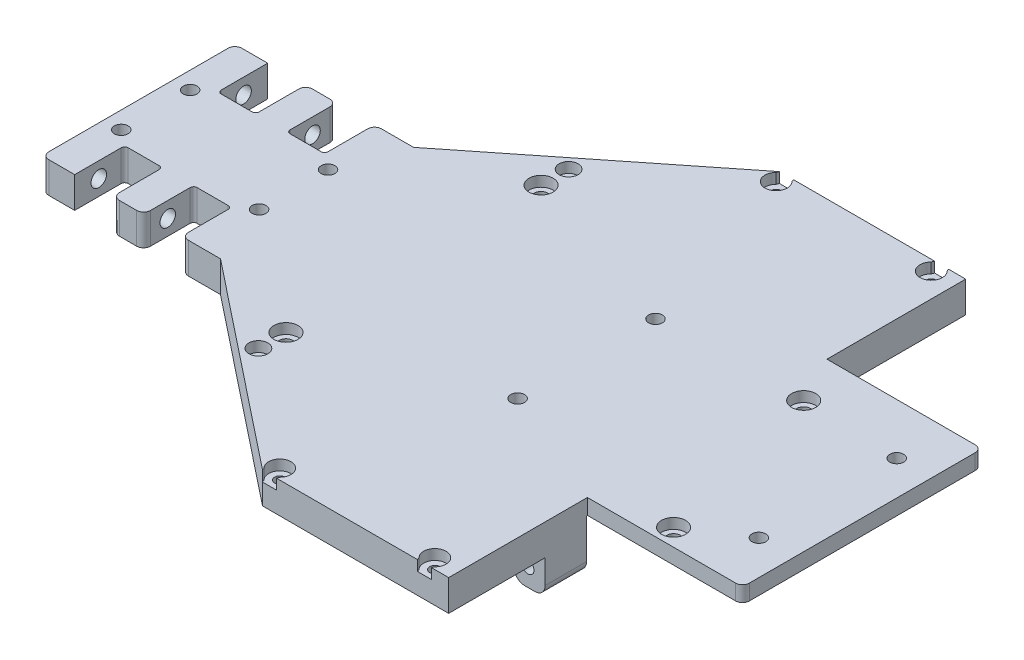
SolidWorks part; units mm, degrees
ref_plane "Front Plane" through (0, 0, 0) normal (0, 0, 1) x (1, 0, 0)
ref_plane "Top Plane" through (0, 0, 0) normal (0, 1, 0) x (1, 0, 0)
ref_plane "Right Plane" through (0, 0, 0) normal (1, 0, 0) x (0, 0, -1)
sketch "Sketch1" plane through (0, 0, 0) normal (0, 1, 0) x (1, 0, 0)
  line L0 (-78.0026, 25) -> (-28.0026, 25)
  line L1 (1.9974, 75) -> (86.9974, 75)
  line L2 (-78.0026, 25) -> (-78.0026, -25)
  line L3 (1.9974, -75) -> (86.9974, -75)
  line L4 (86.9974, 75) -> (86.9974, -75)
  line L7 (-28.0026, 25) -> (1.9974, 75)
  line L8 (1.9974, -75) -> (-28.0026, -25)
  line L9 (-28.0026, -25) -> (-78.0026, -25)
  point P0 (0, 0)
  dimension "D1" = 30
  dimension "D2" = 30
  dimension "D3" = 50
  dimension "D4" = 50
  dimension "D5" = 50
  dimension "D6" = 165
  dimension "D7" = 75
  dimension "D8" = 50
  dimension "D9" = 50
  dimension "D10" = 150
extrude "Boss-Extrude1" add sketch "Sketch1" along normal blind 9
sketch "Sketch3" plane through (0, 9, 0) normal (0, 1, 0) x (1, 0, 0)
  line L1 (-28.0026, 25) -> (-78.0026, 25) construction
  line L4 (-78.0026, 25) -> (-78.0026, -25) construction
  circle A0 centre (-73.0026, 10) radius 2
  circle A1 centre (-33.0026, 10) radius 2
  circle A2 centre (-33.0026, -10) radius 2
  circle A3 centre (-73.0026, -10) radius 2
  dimension "D5" = 4
  dimension "D6" = 4
  dimension "D7" = 4
  dimension "D8" = 4
  dimension "D1" = 40
  dimension "D2" = 20
  dimension "D3" = 20
  dimension "D4" = 40
  dimension "D9" = 15
  dimension "D10" = 5
  dimension "D11" = 15
  dimension "D12" = 5
extrude "Cut-Extrude1" cut sketch "Sketch3" against normal through all
sketch "Sketch4" plane through (86.9974, 0, 0) normal (1, 0, 0) x (0, 0, -1)
  line L0 (-75, 9) -> (75, 9) construction
  line L1 (-34.75, 9) -> (34.75, 9)
  line L2 (-34.75, 9) -> (-34.75, 4.5)
  line L3 (-34.75, 4.5) -> (34.75, 4.5)
  line L4 (34.75, 9) -> (34.75, 4.5)
  line L5 (-75, 9) -> (-75, 0) construction
  line L6 (75, 9) -> (75, 0) construction
  dimension "D1" = 4.5
  dimension "D2" = 40.25
  dimension "D3" = 40.25
extrude "Boss-Extrude2" add sketch "Sketch4" along normal blind 45
sketch "Sketch5" plane through (86.9974, 0, 0) normal (1, 0, 0) x (0, 0, -1)
  line L1 (-35, 4.5) -> (35, 4.5)
  line L2 (-35, 4.5) -> (-35, 0)
  line L3 (-35, 0) -> (35, 0)
  line L4 (35, 4.5) -> (35, 0)
  line L5 (34.75, 4.5) -> (34.75, 9) construction
  dimension "D1" = 70
  dimension "D2" = 0.25
extrude "Cut-Extrude2" cut sketch "Sketch5" against normal blind 50
sketch "Sketch6" plane through (0, 9, 0) normal (0, 1, 0) x (1, 0, 0)
  line L2 (131.9974, 34.75) -> (131.9974, -34.75) construction
  circle A0 centre (51.9974, 20) radius 2
  circle A1 centre (51.9974, -20) radius 2
  circle A2 centre (121.9974, 20) radius 2
  circle A3 centre (121.9974, -20) radius 2
  dimension "D1" = 4
  dimension "D2" = 4
  dimension "D3" = 4
  dimension "D4" = 4
  dimension "D8" = 70
  dimension "D9" = 0
  dimension "D11" = 10
  dimension "D5" = 10
  dimension "D10" = 40
  dimension "D6" = 20
  dimension "D7" = 40
  dimension "D12" = 20
  dimension "D13" = 70
extrude "Cut-Extrude4" cut sketch "Sketch6" against normal blind 50
fillet "Fillet1" radius 2 2 edges at (-28.0026, 4.5, -25) (-28.0026, 4.5, 25)
fillet "Fillet2" radius 2 2 edges at (131.9974, 6.75, -34.75) (131.9974, 6.75, 34.75)
sketch "Sketch7" plane through (0, 9, 0) normal (0, 1, 0) x (1, 0, 0)
  line L0 (-78.0026, -25) -> (-29.1349, -25) construction
  line L1 (-68.5026, -25) -> (-57.5026, -25)
  line L2 (-68.5026, -25) -> (-68.5026, -13.5)
  line L3 (-68.5026, -13.5) -> (-57.5026, -13.5)
  line L4 (-57.5026, -25) -> (-57.5026, -13.5)
  line L5 (-78.0026, 25) -> (-78.0026, -25) construction
  line L6 (-48.5026, -25) -> (-37.5026, -25)
  line L7 (-48.5026, -25) -> (-48.5026, -13.5)
  line L8 (-48.5026, -13.5) -> (-37.5026, -13.5)
  line L9 (-37.5026, -25) -> (-37.5026, -13.5)
  dimension "D1" = 9.5
  dimension "D2" = 11
  dimension "D3" = 9
  dimension "D4" = 11
  dimension "D5" = 11.5
  dimension "D6" = 11.5
extrude "Cut-Extrude5" cut sketch "Sketch7" against normal through all
sketch "Sketch8" plane through (-78.0026, 0, 0) normal (-1, 0, 0) x (0, 0, 1)
  line L0 (-25, 9) -> (25, 9) construction
  line L1 (25, 9) -> (25, 0) construction
  circle A0 centre (21, 4.5) radius 2.25
  dimension "D2" = 4.5
  dimension "D1" = 4.5
  dimension "D3" = 4
extrude "Cut-Extrude6" cut sketch "Sketch8" against normal blind 50
sketch "Sketch10" plane through (-78.0026, 0, 0) normal (-1, 0, 0) x (0, 0, 1)
  circle A0 centre (21, 4.5) radius 3.5
  dimension "D1" = 7
extrude "Cut-Extrude8" cut sketch "Sketch10" against normal blind 4
sketch "Sketch11" plane through (-37.5026, 0, 0) normal (-1, 0, 0) x (0, 0, 1)
  line L33 (17.0163, 4.5) -> (17.0163, -4.7197)
  line L34 (24.9837, 4.5) -> (22.9919, 7.95)
  line L35 (22.9919, 7.95) -> (19.0081, 7.95)
  line L36 (19.0081, 7.95) -> (17.0163, 4.5)
  line L40 (17.0163, -4.7197) -> (24.9837, -4.7197)
  line L41 (24.9837, -4.7197) -> (24.9837, 4.5)
  line L43 (22.9919, 1.05) -> (23.9878, 2.775) [skipped]
  line L44 (19.0081, 1.05) -> (21, 1.05) [skipped]
  line L45 (17.0163, 4.5) -> (18.0122, 2.775) [skipped]
  arc A1 (23.9878, 6.225) -> (18.0122, 6.225) centre (21, 4.5) ccw construction
extrude "Cut-Extrude9" cut sketch "Sketch11" against normal blind 5 from offset 3 offset against normal yes
mirror "Mirror8" about plane through (0, 0, 0) normal (0, 0, 1) of "Cut-Extrude9", "Cut-Extrude8", "Cut-Extrude6", "Cut-Extrude5"
fillet "Fillet6" radius 1 8 edges at (-57.5026, 4.5, 13.5) (-48.5026, 4.5, 13.5) (-37.5026, 4.5, 13.5) (-68.5026, 4.5, 13.5) (-68.5026, 4.5, -13.5) (-57.5026, 4.5, -13.5) (-48.5026, 4.5, -13.5) (-37.5026, 4.5, -13.5)
sketch "Sketch12" plane through (0, 0, 0) normal (0, -1, 0) x (1, 0, 0)
  line L4 (1.9974, 75) -> (86.9974, 75) construction
  line L6 (86.9974, 75) -> (86.9974, 35) construction
  line L7 (4.95, 0) -> (-4.95, 0) construction
  circle A0 centre (34.9974, 72) radius 1.5
  circle A1 centre (79.9974, 72) radius 1.5
  circle A4 centre (79.9974, -72) radius 1.5
  circle A5 centre (34.9974, -72) radius 1.5
  dimension "D4" = 3
  dimension "D6" = 3
  dimension "D3" = 3
  dimension "D5" = 3
  dimension "D7" = 7
  dimension "D8" = 45
extrude "Cut-Extrude10" cut sketch "Sketch12" against normal blind 10
sketch "Sketch13" plane through (0, 9, 0) normal (0, 1, 0) x (1, 0, 0)
  line L0 (-4.95, 0) -> (4.95, 0) construction
  circle A1 centre (34.9974, 72) radius 3.25
  circle A2 centre (79.9974, 72) radius 3.25
  circle A3 centre (79.9974, -72) radius 3.25
  circle A4 centre (34.9974, -72) radius 3.25
  dimension "D1" = 6.5
  dimension "D2" = 6.5
extrude "Cut-Extrude11" cut sketch "Sketch13" against normal blind 3
chamfer "Chamfer1" distance 1 angle 45 8 edges at (81.2474, 7.5, 75) (78.7474, 7.5, 75) (36.2474, 7.5, 75) (33.7474, 7.5, 75) (81.2474, 7.5, -75) (78.7474, 7.5, -75) (36.2474, 7.5, -75) (33.7474, 7.5, -75) first distance on face at (79.9974, 7.5, 71.875) first distance on face at (34.9974, 7.5, 71.875) first distance on face at (79.9974, 7.5, -71.875) first distance on face at (34.9974, 7.5, -71.875)
sketch "Sketch14" plane through (0, 0, 25) normal (0, 0, 1) x (1, 0, 0)
  line L1 (-37.5026, 9) -> (-25.5026, 9)
  line L2 (-37.5026, 9) -> (-37.5026, 0)
  line L3 (-37.5026, 0) -> (-25.5026, 0)
  line L4 (-25.5026, 9) -> (-25.5026, 0)
  dimension "D1" = 12
extrude "Boss-Extrude3" add sketch "Sketch14" along normal blind 3
mirror "Mirror10" about plane through (0, 0, 0) normal (0, 0, 1) of "Boss-Extrude3"
sketch "Sketch15" plane through (0, 4.5, 0) normal (0, -1, 0) x (1, 0, 0)
  line L0 (131.9974, 32.75) -> (131.9974, -32.75) construction
  line L1 (129.9974, 34.75) -> (86.9974, 34.75) construction
  line L2 (86.9974, -75) -> (1.9974, -75) construction
  line L3 (86.9974, -35) -> (86.9974, -75) construction
  circle A0 centre (93.9974, -21) radius 2
  circle A1 centre (106.9974, 29.75) radius 2
  dimension "D3" = 4
  dimension "D5" = 4
  dimension "D1" = 54
  dimension "D2" = 7
  dimension "D4" = 25
  dimension "D6" = 5
extrude "Cut-Extrude12" cut sketch "Sketch15" against normal through all
sketch "Sketch16" plane through (0, 0, 0) normal (0, -1, 0) x (1, 0, 0)
  line L1 (86.9974, -75) -> (1.9974, -75) construction
  line L2 (4.95, 0) -> (-4.95, 0) construction
  circle A0 centre (1.7974, -37) radius 2
  circle A2 centre (1.7974, -45) radius 1.5
  circle A3 centre (1.7974, 45) radius 1.5
  circle A4 centre (1.7974, 37) radius 2
  dimension "D1" = 4
  dimension "D2" = 0
  dimension "D8" = 3
  dimension "D4" = 38
  dimension "D5" = 28
  dimension "D7" = 8
extrude "Cut-Extrude13" cut sketch "Sketch16" against normal blind 10
sketch "Sketch17" plane through (0, 0, 0) normal (0, -1, 0) x (1, 0, 0)
  line L0 (1.9974, 75) -> (86.9974, 75) construction
  line L1 (27.9974, 47) -> (36.9974, 47)
  line L2 (27.9974, 47) -> (27.9974, 35)
  line L3 (27.9974, 35) -> (36.9974, 35)
  line L4 (36.9974, 47) -> (36.9974, 35)
  line L5 (77.9974, 47) -> (86.9974, 47)
  line L6 (77.9974, 47) -> (77.9974, 35)
  line L7 (77.9974, 35) -> (86.9974, 35)
  line L8 (86.9974, 47) -> (86.9974, 35)
  line L9 (86.9974, 75) -> (86.9974, 35) construction
  dimension "D1" = 9
  dimension "D2" = 9
  dimension "D3" = 41
  dimension "D4" = 12
  dimension "D5" = 12
  dimension "D6" = 28
  dimension "D7" = 0
  dimension "D8" = 28
extrude "Boss-Extrude4" add sketch "Sketch17" along normal blind 10
sketch "Sketch18" plane through (0, 0, 47) normal (0, 0, 1) x (1, 0, 0)
  line L0 (27.9974, -10) -> (27.9974, 0) construction
  line L1 (77.9974, -10) -> (77.9974, 0) construction
  circle A0 centre (32.9974, -4.8167) radius 1.75
  circle A1 centre (81.9974, -4.8167) radius 1.75
  dimension "D2" = 3.5
  dimension "D4" = 3.5
  dimension "D1" = 5
  dimension "D3" = 4
extrude "Cut-Extrude14" cut sketch "Sketch18" against normal through all
fillet "Fillet8" radius 3 6 edges at (27.9974, 0, 41) (32.4974, 0, 35) (36.9974, -10, 41) (27.9974, -10, 41) (77.9974, -10, 41) (86.9974, -10, 41)
chamfer "Chamfer2" distance 0.5 angle 45 12 edges at (79.9974, 0, 70.5) (79.9974, 0, -70.5) (34.9974, 0, -70.5) (1.7974, 0, -46.5) (1.7974, 0, -39) (-73.0026, 0, -8) (-73.0026, 0, 12) (-33.0026, 0, 12) (-33.0026, 0, -8) (1.7974, 0, 46.5) (34.9974, 0, 70.5) (1.7974, 0, 39)
sketch "Sketch19" plane through (0, 9, 0) normal (0, 1, 0) x (1, 0, 0)
  circle A0 centre (1.7974, 45) radius 2.75
  circle A1 centre (1.7974, -45) radius 2.75
  circle A2 centre (1.7974, -37) radius 3.5
  circle A3 centre (106.9974, -29.75) radius 3.5
  circle A4 centre (1.7974, 37) radius 3.5
  circle A5 centre (93.9974, 21) radius 3.5
  dimension "D1" = 7
  dimension "D2" = 5.5
  dimension "D3" = 5.5
  dimension "D4" = 7
  dimension "D5" = 7
  dimension "D6" = 7
extrude "Cut-Extrude15" cut sketch "Sketch19" against normal blind 3
sketch "Sketch20" plane through (0, 0, -25) normal (0, 0, -1) x (-1, 0, 0)
  line L1 (57.5026, 0) -> (48.5026, 0)
  line L2 (57.5026, 0) -> (57.5026, 9)
  line L3 (57.5026, 9) -> (48.5026, 9)
  line L4 (48.5026, 0) -> (48.5026, 9)
  line L5 (68.5026, 9) -> (78.0026, 9)
  line L6 (68.5026, 9) -> (68.5026, 0)
  line L7 (68.5026, 0) -> (78.0026, 0)
  line L8 (78.0026, 9) -> (78.0026, 0)
extrude "Boss-Extrude5" add sketch "Sketch20" along normal blind 3
mirror "Mirror11" about plane through (0, 0, 0) normal (0, 0, 1) of "Boss-Extrude5"
fillet "Fillet9" radius 2 8 edges at (-37.5026, 4.5, 28) (-48.5026, 4.5, 28) (-57.5026, 4.5, 28) (-48.5026, 4.5, -28) (-57.5026, 4.5, -28) (-37.5026, 4.5, -28) (-78.0026, 4.5, 28) (-78.0026, 4.5, -28)
sketch "Sketch21" plane through (0, 0, 0) normal (0, -1, 0) x (1, 0, 0)
  line L0 (-26.2026, 28) -> (32.9974, 75)
  line L1 (32.9974, -75) -> (-26.2026, -28)
  line L2 (86.9974, -75) -> (1.9974, -75) construction
  line L3 (86.9974, -35) -> (86.9974, -75) construction
  line L4 (86.9974, 75) -> (86.9974, 47) construction
  line L5 (-26.2026, -28) -> (1.9974, -75)
  line L6 (1.9974, -75) -> (32.9974, -75)
  line L7 (-26.2026, 28) -> (1.9974, 75)
  line L8 (1.9974, 75) -> (32.9974, 75)
  dimension "D1" = 54
  dimension "D2" = 54
  dimension "D3" = 38.447
extrude "Cut-Extrude16" cut sketch "Sketch21" against normal blind 10
equation "\"D2@Sketch6\"=\"D4@Sketch6\""
equation "\"D5@Sketch7\"=\"D6@Sketch7\""
equation "\"D3@Sketch4\"=\"D2@Sketch4\""
